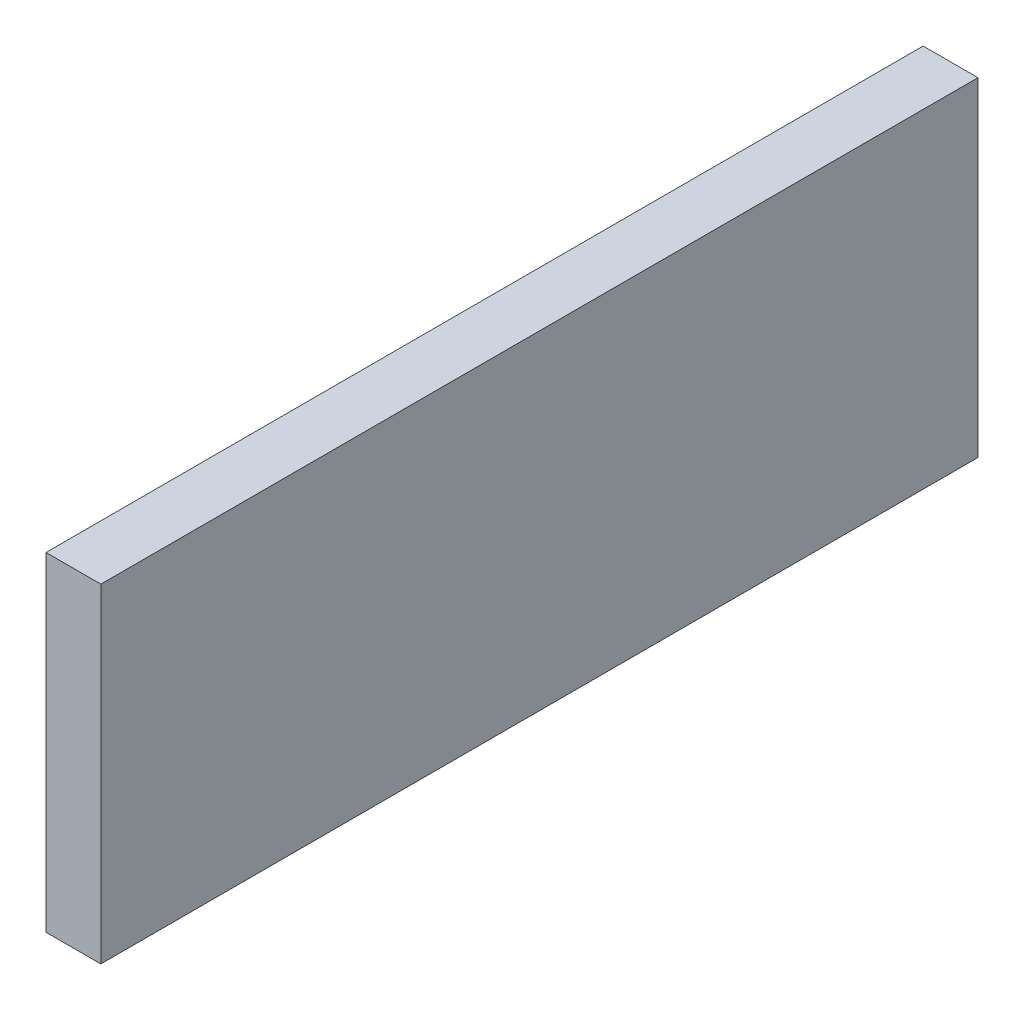
SolidWorks part; units mm, degrees
ref_plane "Front Plane" through (0, 0, 0) normal (1, 0, 0) x (0, 1, 0)
ref_plane "Top Plane" through (0, 0, 0) normal (0, 0, 1) x (0, 1, 0)
ref_plane "Right Plane" through (0, 0, 0) normal (0, 1, 0) x (-1, 0, 0)
sketch "Sketch1" plane through (0, 0, 0) normal (1, 0, 0) x (0, 1, 0)
  line L0 (-15, 0) -> (15, 0) construction
  line L1 (-15, 40) -> (15, 40)
  line L2 (-15, 40) -> (-15, -40)
  line L3 (-15, -40) -> (15, -40)
  line L4 (15, 40) -> (15, -40)
  line L5 (-15, 40) -> (15, -40) construction
  line L6 (-15, -40) -> (15, 40) construction
  circle A0 centre (0, 15.35) radius 4.8
  circle A1 centre (0, -15.35) radius 4.8
  point P0 (0, 0)
  dimension "D3" = 9.6
  dimension "D1" = 30
  dimension "D2" = 80
  dimension "D4" = 30.7
extrude "Boss-Extrude1" add sketch "Sketch1" along normal blind 5 contours A0 | A1 | L4 L1 L2 L3 A1 A0 region at (0, 0, 0) region at (0, 0, 15.35) region at (0, 0, -15.35)
extrude "Boss-Extrude2" add sketch "Sketch1<3>" against normal blind 5 contours A0 | A1
sketch "Sketch1<3>" plane through (0, 0, 0) normal (1, 0, 0) x (0, 1, 0) same geometry as "Sketch1"
